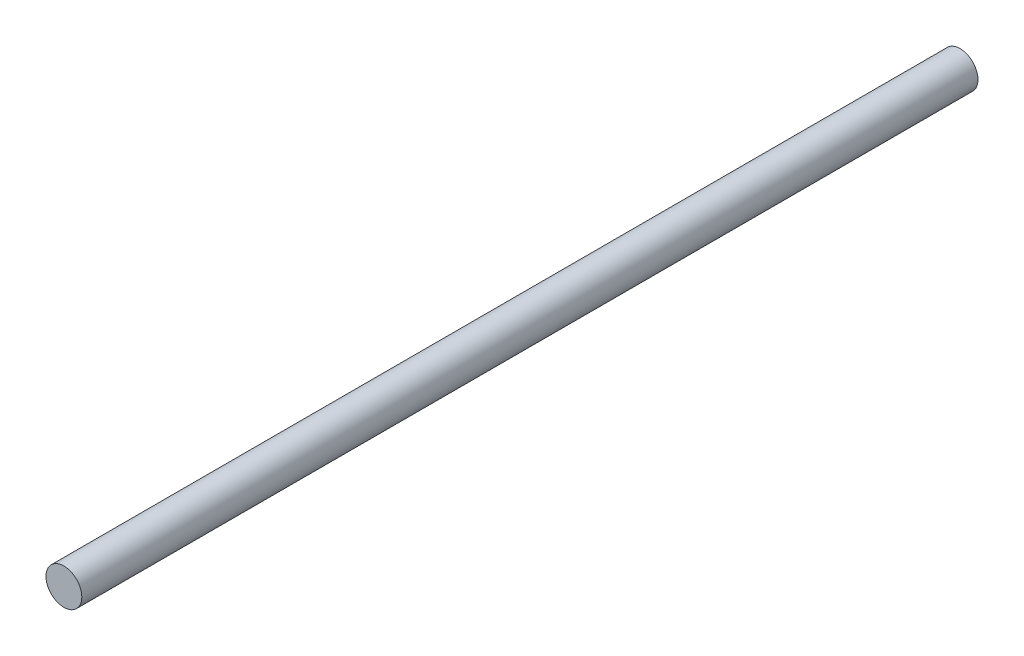
SolidWorks part; units mm, degrees
ref_plane "Ebene vorne" through (0, 0, 0) normal (0, 0, 1) x (1, 0, 0)
ref_plane "Ebene oben" through (0, 0, 0) normal (0, 1, 0) x (1, 0, 0)
ref_plane "Ebene rechts" through (0, 0, 0) normal (1, 0, 0) x (0, 0, -1)
sketch "Skizze1" plane through (0, 0, 0) normal (0, 0, 1) x (1, 0, 0)
  circle A0 centre (0, 0) radius 10
extrude "Aufsatz-Linear austragen1" add sketch "Skizze1" along normal blind 500
